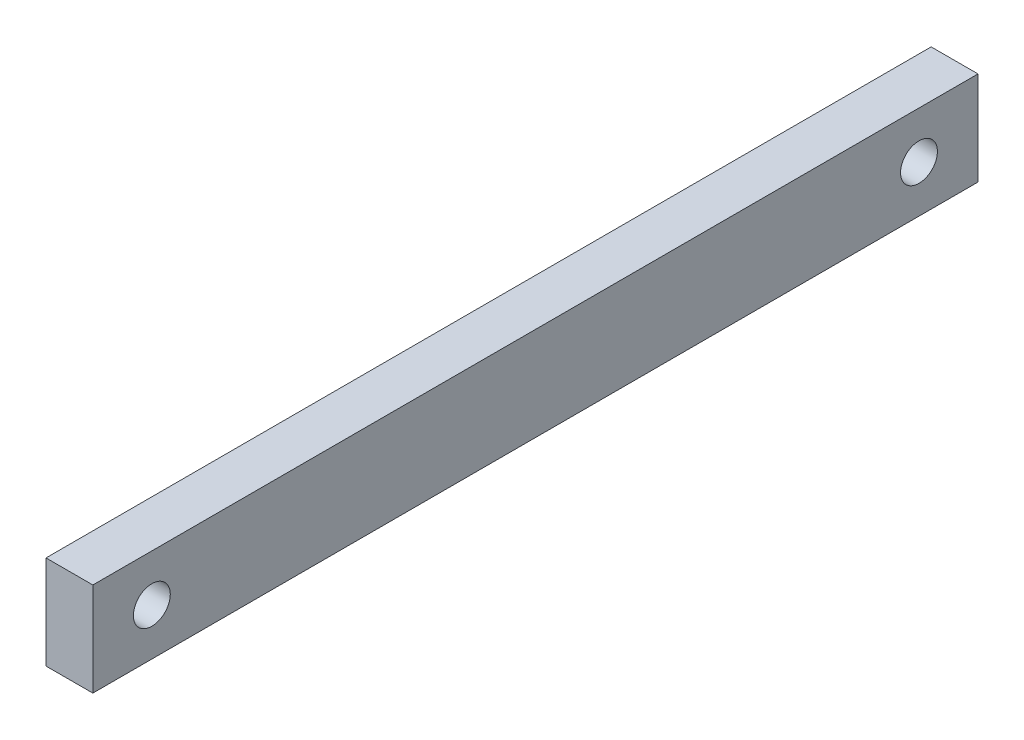
SolidWorks part; units mm, degrees
ref_plane "Front Plane" through (0, 0, 0) normal (0, 0, 1) x (1, 0, 0)
ref_plane "Top Plane" through (0, 0, 0) normal (0, 1, 0) x (1, 0, 0)
ref_plane "Right Plane" through (0, 0, 0) normal (1, 0, 0) x (0, 0, -1)
sketch "Sketch2" plane through (0, 0, 0) normal (0, 0, 1) x (1, 0, 0)
  line L1 (-3.175, -6.35) -> (3.175, -6.35)
  line L2 (-3.175, -6.35) -> (-3.175, 6.35)
  line L3 (-3.175, 6.35) -> (3.175, 6.35)
  line L4 (3.175, -6.35) -> (3.175, 6.35)
  line L5 (-3.175, -6.35) -> (3.175, 6.35) construction
  line L6 (-3.175, 6.35) -> (3.175, -6.35) construction
  point P0 (0, 0)
  dimension "D1" = 6.35
  dimension "D2" = 12.7
extrude "Boss-Extrude1" add sketch "Sketch2" along normal blind 60 and the other way blind 60
sketch "Sketch4" plane through (3.175, 0, 0) normal (1, 0, 0) x (0, 0, -1)
  line L0 (0, 0) -> (0, -6.35) construction
  line L1 (60, -6.35) -> (-60, -6.35) construction
  line L2 (-60, -6.35) -> (-60, 6.35) construction
  circle A0 centre (-52, 0) radius 2.5
  circle A1 centre (52, 0) radius 2.5
  dimension "D1" = 5
  dimension "D2" = 8
extrude "Cut-Extrude1" cut sketch "Sketch4" against normal through all
